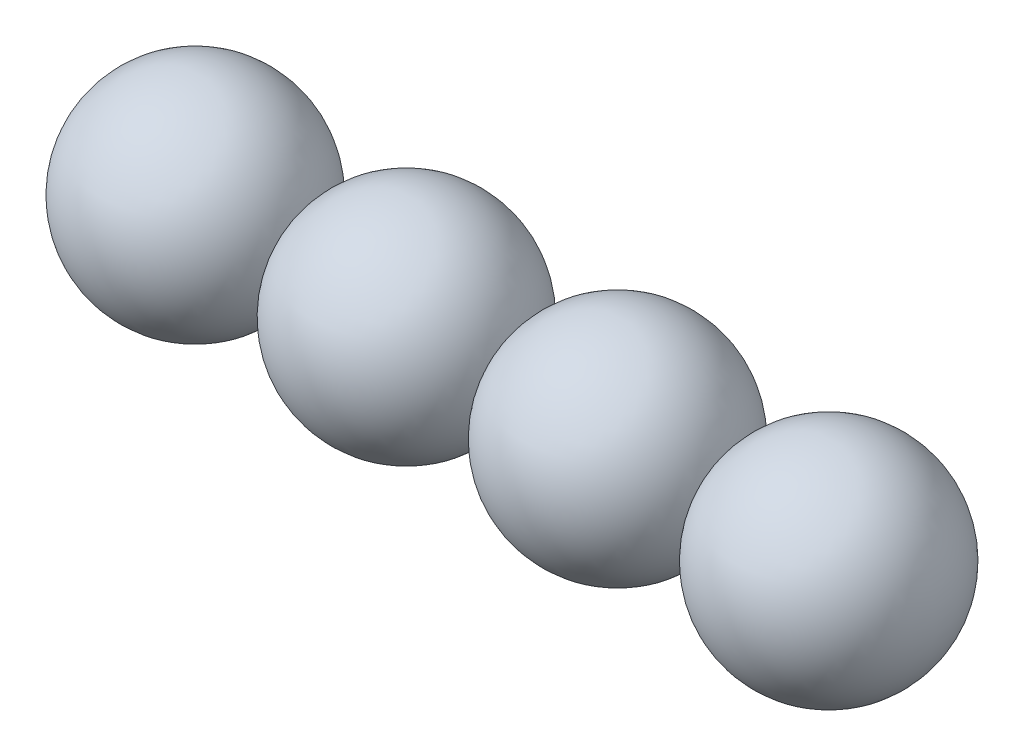
SolidWorks part; units mm, degrees
ref_plane "前基準面" through (0, 0, 0) normal (0, 0, 1) x (1, 0, 0)
ref_plane "上基準面" through (0, 0, 0) normal (0, 1, 0) x (1, 0, 0)
ref_plane "右基準面" through (0, 0, 0) normal (1, 0, 0) x (0, 0, -1)
sketch "草圖1" plane through (0, 0, 0) normal (0, 0, 1) x (1, 0, 0)
  line L0 (0, 30) -> (0, -57.2417)
  line L1 (0, 30) -> (0, -30)
  line L2 (60, 30) -> (60, -30)
  line L3 (120, 30) -> (120, -30)
  line L4 (60, 30) -> (60, -63.2368)
  line L5 (180, 0) -> (228.3593, 0)
  line L6 (60, -63.2368) -> (60, -30)
  line L7 (120, -30) -> (120, -48.9727)
  line L8 (120, -48.9727) -> (120, -30)
  line L9 (180, 30) -> (180, -58.9066) construction
  line L10 (120.355, 18.9908) -> (120.355, -41.0092)
  line L11 (180, 30) -> (180, -30)
  arc A0 (0, -30) -> (0, 30) centre (0, 0) ccw
  arc A1 (60, -30) -> (60, 30) centre (60, 0) ccw
  arc A2 (120, -30) -> (120, 30) centre (120, 0) ccw
  arc A3 (180, -30) -> (180, 30) centre (180, 0) ccw
  dimension "D1" = 60
  dimension "D2" = 60
  dimension "D3" = 60
  dimension "D4" = 60
  dimension "D5" = 60
  dimension "D6" = 60
revolve "旋轉1" add sketch "草圖1" angle 360 about L0 region at (12.7324, 0, 0)
revolve "旋轉2" add sketch "草圖1<8>" angle 360 about L4 region at (72.7324, 0, 0)
sketch "草圖1<8>" plane through (0, 0, 0) normal (0, 0, 1) x (1, 0, 0) same geometry as "草圖1"
revolve "旋轉3" add sketch "草圖1<9>" angle 360 about L7 region at (132.7324, 0, 0)
sketch "草圖1<9>" plane through (0, 0, 0) normal (0, 0, 1) x (1, 0, 0) same geometry as "草圖1"
revolve "旋轉4" add sketch "草圖1<10>" angle 360 about L9 region at (192.7324, 12.7324, 0) region at (192.7324, -12.7324, 0)
sketch "草圖1<10>" plane through (0, 0, 0) normal (0, 0, 1) x (1, 0, 0) same geometry as "草圖1"
